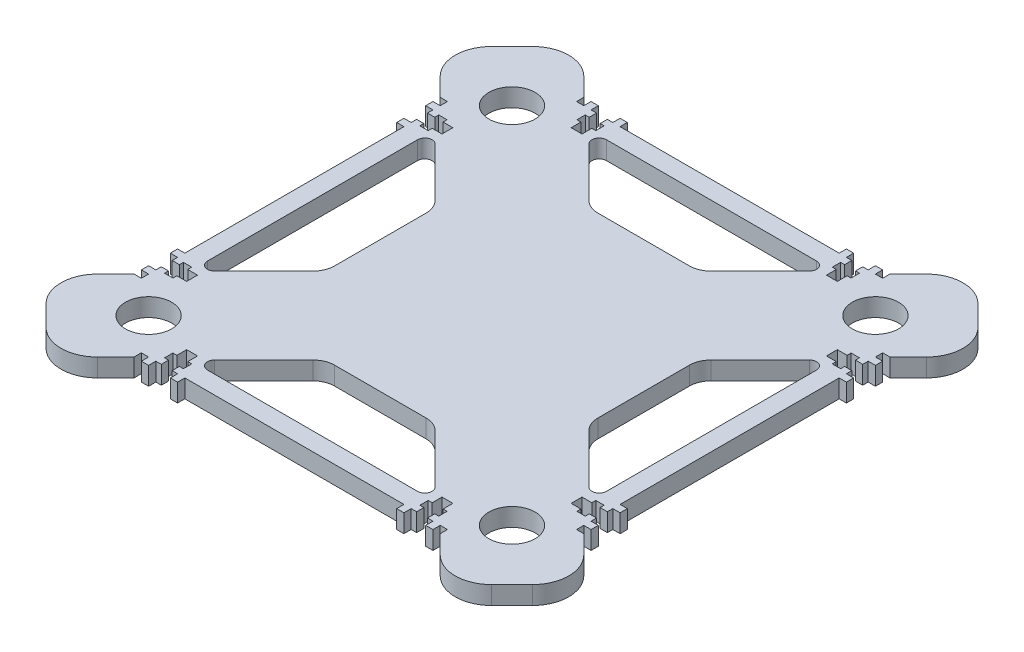
SolidWorks part; units mm, degrees
ref_plane "Front Plane" through (0, 0, 0) normal (0, 0, 1) x (1, 0, 0)
ref_plane "Top Plane" through (0, 0, 0) normal (0, 1, 0) x (1, 0, 0)
ref_plane "Right Plane" through (0, 0, 0) normal (1, 0, 0) x (0, 0, -1)
sketch "Sketch1" plane through (0, 0, 0) normal (0, 1, 0) x (1, 0, 0)
  line L1 (0, 0) -> (120, 0)
  line L2 (0, 0) -> (0, 120)
  line L3 (0, 120) -> (120, 120)
  line L4 (120, 0) -> (120, 120)
  dimension "D1" = 120
  dimension "D2" = 120
extrude "Boss-Extrude1" add sketch "Sketch1" along normal blind 5
sketch "Sketch2" plane through (0, 5, 0) normal (0, 1, 0) x (1, 0, 0)
  line L0 (60, 120) -> (60, 0) construction
  line L1 (120, 120) -> (0, 120) construction
  line L2 (0, 0) -> (120, 0) construction
  line L3 (120, 60) -> (0, 60) construction
  line L4 (120, 0) -> (120, 120) construction
  line L5 (0, 120) -> (0, 0) construction
  line L6 (60, 60) -> (120, 120) construction
  line L7 (110.1005, 110.1005) -> (120, 100.201) construction
  line L8 (110.1005, 110.1005) -> (100.201, 120) construction
  line L9 (100.201, 120) -> (120, 100.201)
  line L10 (100.201, 120) -> (114.3431, 134.1421)
  line L11 (120, 100.201) -> (134.1421, 114.3431)
  line L12 (114.3431, 134.1421) -> (134.1421, 114.3431)
  line L13 (0, 100.201) -> (-14.1421, 114.3431)
  line L14 (5.6569, 134.1421) -> (-14.1421, 114.3431)
  line L15 (19.799, 120) -> (5.6569, 134.1421)
  line L16 (19.799, 120) -> (0, 100.201)
  line L17 (19.799, 0) -> (0, 19.799)
  line L18 (19.799, 0) -> (5.6569, -14.1421)
  line L19 (5.6569, -14.1421) -> (-14.1421, 5.6569)
  line L20 (0, 19.799) -> (-14.1421, 5.6569)
  line L21 (120, 19.799) -> (134.1421, 5.6569)
  line L22 (114.3431, -14.1421) -> (134.1421, 5.6569)
  line L23 (100.201, 0) -> (114.3431, -14.1421)
  line L24 (100.201, 0) -> (120, 19.799)
  point P33 (120, 100.201)
  point P34 (100.201, 120)
  dimension "D1" = 28
  dimension "D2" = 20
extrude "Boss-Extrude3" add sketch "Sketch2" against normal blind 5
sketch "Sketch3" plane through (0, 5, 0) normal (0, 1, 0) x (1, 0, 0)
  line L0 (-4.2426, -4.2426) -> (124.2426, 124.2426) construction
  line L1 (-14.1421, 5.6569) -> (5.6569, -14.1421) construction
  line L2 (134.1421, 114.3431) -> (114.3431, 134.1421) construction
  line L3 (0, 19.799) -> (19.799, 0) construction
  line L13 (0, 60) -> (120, 60) construction
  line L14 (0, 100.201) -> (0, 19.799) construction
  line L15 (120, 19.799) -> (120, 100.201) construction
  line L16 (60, 0) -> (60, 120) construction
  line L17 (19.799, 0) -> (100.201, 0) construction
  line L18 (100.201, 120) -> (19.799, 120) construction
  circle A16 centre (9.8995, 9.8995) radius 6.375
  circle A17 centre (110.1005, 9.8995) radius 6.375
  circle A18 centre (9.8995, 110.1005) radius 6.375
  circle A19 centre (110.1005, 110.1005) radius 6.375
  point P10 (9.8995, 9.8995)
  dimension "D1" = 12.75
extrude "Cut-Extrude1" cut sketch "Sketch3" against normal blind 5
sketch "Sketch5" plane through (0, 5, 0) normal (0, 1, 0) x (1, 0, 0)
  line L0 (60, 0) -> (60, 120) construction
  line L1 (19.799, 0) -> (100.201, 0) construction
  line L2 (100.201, 120) -> (19.799, 120) construction
  line L3 (60, 15) -> (65, 15) construction
  line L4 (65, 15) -> (60, 10)
  line L5 (65, 15) -> (60, 5)
  line L6 (55, 15) -> (60, 5)
  line L7 (55, 15) -> (60, 10)
  dimension "D1" = 5
  dimension "D2" = 5
  dimension "D3" = 10
  dimension "D4" = 5
extrude "Cut-Extrude3" cut sketch "Sketch5" against normal blind 5
sketch "Sketch6" plane through (0, 5, 0) normal (0, 1, 0) x (1, 0, 0)
  line L0 (0, 19.799) -> (0, 17.799)
  line L1 (0, 17.799) -> (-2, 17.799)
  line L2 (0, 19.799) -> (-14.1421, 5.6569) construction
  line L3 (-2, 17.799) -> (0, 19.799)
  line L4 (0, 0) -> (124.2426, 124.2426) construction
  line L5 (134.1421, 114.3431) -> (114.3431, 134.1421) construction
  line L6 (60, 120) -> (60, 0) construction
  line L7 (100.201, 120) -> (19.799, 120) construction
  line L8 (19.799, 0) -> (100.201, 0) construction
  line L9 (0, 60) -> (120, 60) construction
  line L10 (0, 100.201) -> (0, 19.799) construction
  line L11 (120, 19.799) -> (120, 100.201) construction
  line L12 (17.799, -2) -> (19.799, 0)
  line L13 (17.799, 0) -> (17.799, -2)
  line L14 (19.799, 0) -> (17.799, 0)
  line L15 (100.201, 0) -> (102.201, 0)
  line L16 (102.201, 0) -> (102.201, -2)
  line L17 (102.201, -2) -> (100.201, 0)
  line L18 (122, 17.799) -> (120, 19.799)
  line L19 (120, 17.799) -> (122, 17.799)
  line L20 (120, 19.799) -> (120, 17.799)
  line L21 (120, 100.201) -> (120, 102.201)
  line L22 (120, 102.201) -> (122, 102.201)
  line L23 (122, 102.201) -> (120, 100.201)
  line L24 (102.201, 122) -> (100.201, 120)
  line L25 (102.201, 120) -> (102.201, 122)
  line L26 (100.201, 120) -> (102.201, 120)
  line L27 (19.799, 120) -> (17.799, 120)
  line L28 (17.799, 120) -> (17.799, 122)
  line L29 (17.799, 122) -> (19.799, 120)
  line L30 (-2, 102.201) -> (0, 100.201)
  line L31 (0, 102.201) -> (-2, 102.201)
  line L32 (0, 100.201) -> (0, 102.201)
  dimension "D1" = 2
extrude "Cut-Extrude4" cut sketch "Sketch6" against normal blind 10
fillet "Fillet1" radius 10 8 edges at (5.6569, 2.5, 14.1421) (-14.1421, 2.5, -5.6569) (-14.1421, 2.5, -114.3431) (5.6569, 2.5, -134.1421) (114.3431, 2.5, -134.1421) (134.1421, 2.5, -114.3431) (134.1421, 2.5, -5.6569) (114.3431, 2.5, 14.1421)
sketch "Sketch7" plane through (0, 5, 0) normal (0, 1, 0) x (1, 0, 0)
  line L0 (0, 60) -> (120, 60) construction
  line L1 (0, 102.201) -> (0, 17.799) construction
  line L2 (120, 17.799) -> (120, 102.201) construction
  line L3 (60, 120) -> (60, 0) construction
  line L4 (102.201, 120) -> (17.799, 120) construction
  line L5 (17.799, 0) -> (102.201, 0) construction
  line L7 (23.6951, 44.9084) -> (23.6951, 75.0916)
  line L8 (23.6951, 75.0916) -> (5, 93.7868)
  line L9 (5, 93.7868) -> (5, 26.2132)
  line L10 (96.3049, 44.9084) -> (115, 26.2132)
  line L12 (23.6951, 44.9084) -> (5, 26.2132)
  line L13 (115, 93.7868) -> (115, 26.2132)
  line L14 (96.3049, 75.0916) -> (115, 93.7868)
  line L15 (96.3049, 44.9084) -> (96.3049, 75.0916)
  line L18 (75.0916, 96.3049) -> (93.7868, 115)
  line L19 (93.7868, 115) -> (26.2132, 115)
  line L20 (44.9083, 96.3049) -> (26.2132, 115)
  line L21 (44.9083, 96.3049) -> (75.0916, 96.3049)
  line L22 (44.9084, 23.6951) -> (26.2132, 5)
  line L23 (93.7868, 5) -> (26.2132, 5)
  line L24 (75.0917, 23.6951) -> (93.7868, 5)
  line L25 (44.9084, 23.6951) -> (75.0917, 23.6951)
  point P29 (115, 60)
  point P30 (96.3049, 60)
  point P43 (60, 5)
  point P44 (60, 23.6951)
extrude "Cut-Extrude5" cut sketch "Sketch7" against normal blind 10
fillet "Fillet2" radius 2 8 edges at (115, 2.5, -26.2132) (115, 2.5, -93.7868) (93.7868, 2.5, -115) (26.2132, 2.5, -115) (26.2132, 2.5, -5) (93.7868, 2.5, -5) (5, 2.5, -26.2132) (5, 2.5, -93.7868)
fillet "Fillet3" radius 6 8 edges at (44.9083, 2.5, -96.3049) (75.0916, 2.5, -96.3049) (23.6951, 2.5, -75.0916) (23.6951, 2.5, -44.9084) (75.0917, 2.5, -23.6951) (44.9084, 2.5, -23.6951) (96.3049, 2.5, -44.9084) (96.3049, 2.5, -75.0916)
sketch "Sketch8" plane through (0, 5, 0) normal (0, 1, 0) x (1, 0, 0)
  line L0 (60, 0) -> (60, 120) construction
  line L1 (17.799, 0) -> (102.201, 0) construction
  line L2 (102.201, 120) -> (17.799, 120) construction
  line L3 (0, 60) -> (120, 60) construction
  line L4 (0, 102.201) -> (0, 17.799) construction
  line L5 (120, 17.799) -> (120, 102.201) construction
  line L6 (-4.2426, 124.2426) -> (124.2426, -4.2426) construction
  line L7 (-1.4142, 127.0711) -> (-7.0711, 121.4142) construction
  line L8 (121.4142, -7.0711) -> (127.0711, -1.4142) construction
  line L9 (24.799, 0) -> (24.799, 7) construction
  line L10 (23.299, 2) -> (23.299, 0)
  line L11 (26.299, 7) -> (23.299, 7)
  line L12 (26.299, 7) -> (26.299, 4.3)
  line L13 (26.299, 0) -> (23.299, 0)
  line L14 (23.299, 7) -> (23.299, 4.3)
  line L15 (26.299, 7) -> (23.299, 0) construction
  line L16 (26.299, 0) -> (23.299, 7) construction
  line L17 (23.299, 2) -> (22.199, 2)
  line L19 (23.299, 4.3) -> (22.199, 4.3)
  line L20 (22.199, 2) -> (22.199, 4.3)
  line L21 (26.299, 4.3) -> (27.399, 4.3)
  line L22 (27.399, 2) -> (27.399, 4.3)
  line L23 (26.299, 2) -> (27.399, 2)
  line L24 (26.299, 2) -> (26.299, 0)
  line L25 (17.799, 0) -> (17.799, -2) construction
  line L26 (93.701, 0) -> (96.701, 7) construction
  line L27 (93.701, 7) -> (96.701, 0) construction
  line L28 (95.201, 0) -> (95.201, 7) construction
  line L29 (93.701, 2) -> (93.701, 0)
  line L30 (93.701, 2) -> (92.601, 2)
  line L31 (92.601, 2) -> (92.601, 4.3)
  line L32 (93.701, 4.3) -> (92.601, 4.3)
  line L33 (97.801, 2) -> (97.801, 4.3)
  line L34 (96.701, 4.3) -> (97.801, 4.3)
  line L35 (96.701, 2) -> (97.801, 2)
  line L36 (96.701, 7) -> (96.701, 4.3)
  line L37 (93.701, 0) -> (96.701, 0)
  line L38 (93.701, 7) -> (93.701, 4.3)
  line L39 (93.701, 7) -> (96.701, 7)
  line L40 (96.701, 2) -> (96.701, 0)
  line L41 (95.201, 120) -> (95.201, 113) construction
  line L42 (93.701, 113) -> (96.701, 120) construction
  line L43 (93.701, 120) -> (96.701, 113) construction
  line L44 (26.299, 120) -> (23.299, 113) construction
  line L45 (26.299, 113) -> (23.299, 120) construction
  line L46 (24.799, 120) -> (24.799, 113) construction
  line L47 (96.701, 118) -> (96.701, 120)
  line L48 (93.701, 113) -> (96.701, 113)
  line L49 (93.701, 113) -> (93.701, 115.7)
  line L50 (93.701, 120) -> (96.701, 120)
  line L51 (96.701, 113) -> (96.701, 115.7)
  line L52 (96.701, 118) -> (97.801, 118)
  line L53 (96.701, 115.7) -> (97.801, 115.7)
  line L54 (97.801, 118) -> (97.801, 115.7)
  line L55 (93.701, 115.7) -> (92.601, 115.7)
  line L56 (92.601, 118) -> (92.601, 115.7)
  line L57 (93.701, 118) -> (92.601, 118)
  line L58 (93.701, 118) -> (93.701, 120)
  line L59 (26.299, 118) -> (26.299, 120)
  line L60 (26.299, 118) -> (27.399, 118)
  line L61 (27.399, 118) -> (27.399, 115.7)
  line L62 (26.299, 115.7) -> (27.399, 115.7)
  line L63 (22.199, 118) -> (22.199, 115.7)
  line L64 (23.299, 115.7) -> (22.199, 115.7)
  line L65 (23.299, 118) -> (22.199, 118)
  line L66 (23.299, 113) -> (23.299, 115.7)
  line L67 (26.299, 120) -> (23.299, 120)
  line L68 (26.299, 113) -> (26.299, 115.7)
  line L69 (26.299, 113) -> (23.299, 113)
  line L70 (23.299, 118) -> (23.299, 120)
  line L71 (0, 95.201) -> (7, 95.201) construction
  line L72 (7, 93.701) -> (0, 96.701) construction
  line L73 (0, 93.701) -> (7, 96.701) construction
  line L74 (0, 26.299) -> (7, 23.299) construction
  line L75 (7, 26.299) -> (0, 23.299) construction
  line L76 (0, 24.799) -> (7, 24.799) construction
  line L77 (120, 24.799) -> (113, 24.799) construction
  line L78 (113, 26.299) -> (120, 23.299) construction
  line L79 (120, 26.299) -> (113, 23.299) construction
  line L80 (120, 93.701) -> (113, 96.701) construction
  line L81 (113, 93.701) -> (120, 96.701) construction
  line L82 (120, 95.201) -> (113, 95.201) construction
  line L83 (2, 96.701) -> (0, 96.701)
  line L84 (7, 93.701) -> (7, 96.701)
  line L85 (7, 93.701) -> (4.3, 93.701)
  line L86 (0, 93.701) -> (0, 96.701)
  line L87 (7, 96.701) -> (4.3, 96.701)
  line L88 (2, 96.701) -> (2, 97.801)
  line L89 (4.3, 96.701) -> (4.3, 97.801)
  line L90 (2, 97.801) -> (4.3, 97.801)
  line L91 (4.3, 93.701) -> (4.3, 92.601)
  line L92 (2, 92.601) -> (4.3, 92.601)
  line L93 (2, 93.701) -> (2, 92.601)
  line L94 (2, 93.701) -> (0, 93.701)
  line L95 (2, 26.299) -> (0, 26.299)
  line L96 (2, 26.299) -> (2, 27.399)
  line L97 (2, 27.399) -> (4.3, 27.399)
  line L98 (4.3, 26.299) -> (4.3, 27.399)
  line L99 (2, 22.199) -> (4.3, 22.199)
  line L100 (4.3, 23.299) -> (4.3, 22.199)
  line L101 (2, 23.299) -> (2, 22.199)
  line L102 (7, 23.299) -> (4.3, 23.299)
  line L103 (0, 26.299) -> (0, 23.299)
  line L104 (7, 26.299) -> (4.3, 26.299)
  line L105 (7, 26.299) -> (7, 23.299)
  line L106 (2, 23.299) -> (0, 23.299)
  line L107 (118, 23.299) -> (120, 23.299)
  line L108 (113, 26.299) -> (113, 23.299)
  line L109 (113, 26.299) -> (115.7, 26.299)
  line L110 (120, 26.299) -> (120, 23.299)
  line L111 (113, 23.299) -> (115.7, 23.299)
  line L112 (118, 23.299) -> (118, 22.199)
  line L113 (115.7, 23.299) -> (115.7, 22.199)
  line L114 (118, 22.199) -> (115.7, 22.199)
  line L115 (115.7, 26.299) -> (115.7, 27.399)
  line L116 (118, 27.399) -> (115.7, 27.399)
  line L117 (118, 26.299) -> (118, 27.399)
  line L118 (118, 26.299) -> (120, 26.299)
  line L119 (118, 93.701) -> (120, 93.701)
  line L120 (118, 93.701) -> (118, 92.601)
  line L121 (118, 92.601) -> (115.7, 92.601)
  line L122 (115.7, 93.701) -> (115.7, 92.601)
  line L123 (118, 97.801) -> (115.7, 97.801)
  line L124 (115.7, 96.701) -> (115.7, 97.801)
  line L125 (118, 96.701) -> (118, 97.801)
  line L126 (113, 96.701) -> (115.7, 96.701)
  line L127 (120, 93.701) -> (120, 96.701)
  line L128 (113, 93.701) -> (115.7, 93.701)
  line L129 (113, 93.701) -> (113, 96.701)
  line L130 (118, 96.701) -> (120, 96.701)
  point P20 (24.799, 3.5)
  point P49 (95.201, 3.5)
  point P78 (95.201, 116.5)
  point P79 (24.799, 116.5)
  point P136 (3.5, 95.201)
  point P137 (3.5, 24.799)
  point P138 (116.5, 24.799)
  point P139 (116.5, 95.201)
  dimension "D1" = 2
  dimension "D2" = 2.3
  dimension "D3" = 7
  dimension "D4" = 7
  dimension "D5" = 3
  dimension "D6" = 1.1
extrude "Cut-Extrude6" cut sketch "Sketch8" against normal blind 10
sketch "Sketch9" plane through (0, 5, 0) normal (0, 1, 0) x (1, 0, 0)
  line L0 (7, 95.201) -> (-3.557, 95.201) construction
  line L1 (7, 93.701) -> (7, 96.701) construction
  line L2 (-4.2426, 124.2426) -> (124.2426, -4.2426) construction
  line L3 (-1.4142, 127.0711) -> (-7.0711, 121.4142) construction
  line L4 (121.4142, -7.0711) -> (127.0711, -1.4142) construction
  line L5 (60, 0) -> (60, 120) construction
  line L6 (26.299, 0) -> (93.701, 0) construction
  line L7 (93.701, 120) -> (26.299, 120) construction
  line L8 (0, 60) -> (120, 60) construction
  line L9 (0, 93.701) -> (0, 26.299) construction
  line L10 (120, 26.299) -> (120, 93.701) construction
  line L11 (0, 102.201) -> (0, 96.701) construction
  line L12 (0, 98.201) -> (-2, 98.201)
  line L13 (0, 98.201) -> (0, 100.201)
  line L14 (0, 100.201) -> (-2, 100.201)
  line L15 (-2, 98.201) -> (-2, 100.201)
  line L16 (0, 90.201) -> (-2, 90.201)
  line L17 (-2, 92.201) -> (-2, 90.201)
  line L18 (0, 92.201) -> (-2, 92.201)
  line L19 (0, 92.201) -> (0, 90.201)
  line L20 (19.799, 120) -> (19.799, 122)
  line L21 (21.799, 122) -> (19.799, 122)
  line L22 (21.799, 120) -> (21.799, 122)
  line L23 (21.799, 120) -> (19.799, 120)
  line L24 (27.799, 120) -> (29.799, 120)
  line L25 (27.799, 120) -> (27.799, 122)
  line L26 (27.799, 122) -> (29.799, 122)
  line L27 (29.799, 120) -> (29.799, 122)
  line L28 (92.201, 120) -> (92.201, 122)
  line L29 (92.201, 122) -> (90.201, 122)
  line L30 (90.201, 120) -> (90.201, 122)
  line L31 (92.201, 120) -> (90.201, 120)
  line L32 (98.201, 120) -> (100.201, 120)
  line L33 (98.201, 120) -> (98.201, 122)
  line L34 (98.201, 122) -> (100.201, 122)
  line L35 (100.201, 120) -> (100.201, 122)
  line L36 (120, 100.201) -> (122, 100.201)
  line L37 (122, 98.201) -> (122, 100.201)
  line L38 (120, 98.201) -> (122, 98.201)
  line L39 (120, 98.201) -> (120, 100.201)
  line L40 (120, 92.201) -> (120, 90.201)
  line L41 (120, 92.201) -> (122, 92.201)
  line L42 (122, 92.201) -> (122, 90.201)
  line L43 (120, 90.201) -> (122, 90.201)
  line L44 (120, 27.799) -> (122, 27.799)
  line L45 (122, 27.799) -> (122, 29.799)
  line L46 (120, 29.799) -> (122, 29.799)
  line L47 (120, 27.799) -> (120, 29.799)
  line L48 (120, 21.799) -> (120, 19.799)
  line L49 (120, 21.799) -> (122, 21.799)
  line L50 (122, 21.799) -> (122, 19.799)
  line L51 (120, 19.799) -> (122, 19.799)
  line L52 (98.201, 0) -> (98.201, -2)
  line L53 (98.201, -2) -> (100.201, -2)
  line L54 (100.201, 0) -> (100.201, -2)
  line L55 (98.201, 0) -> (100.201, 0)
  line L56 (92.201, 0) -> (90.201, 0)
  line L57 (90.201, 0) -> (90.201, -2)
  line L58 (92.201, -2) -> (90.201, -2)
  line L59 (92.201, 0) -> (92.201, -2)
  line L60 (27.799, 0) -> (27.799, -2)
  line L61 (27.799, -2) -> (29.799, -2)
  line L62 (29.799, 0) -> (29.799, -2)
  line L63 (27.799, 0) -> (29.799, 0)
  line L64 (21.799, 0) -> (19.799, 0)
  line L65 (21.799, 0) -> (21.799, -2)
  line L66 (21.799, -2) -> (19.799, -2)
  line L67 (19.799, 0) -> (19.799, -2)
  line L68 (0, 19.799) -> (-2, 19.799)
  line L69 (-2, 21.799) -> (-2, 19.799)
  line L70 (0, 21.799) -> (-2, 21.799)
  line L71 (0, 21.799) -> (0, 19.799)
  line L72 (0, 27.799) -> (0, 29.799)
  line L73 (0, 27.799) -> (-2, 27.799)
  line L74 (-2, 27.799) -> (-2, 29.799)
  line L75 (0, 29.799) -> (-2, 29.799)
  dimension "D1" = 2
  dimension "D2" = 2
  dimension "D3" = 3
extrude "Boss-Extrude4" add sketch "Sketch9" against normal blind 5
